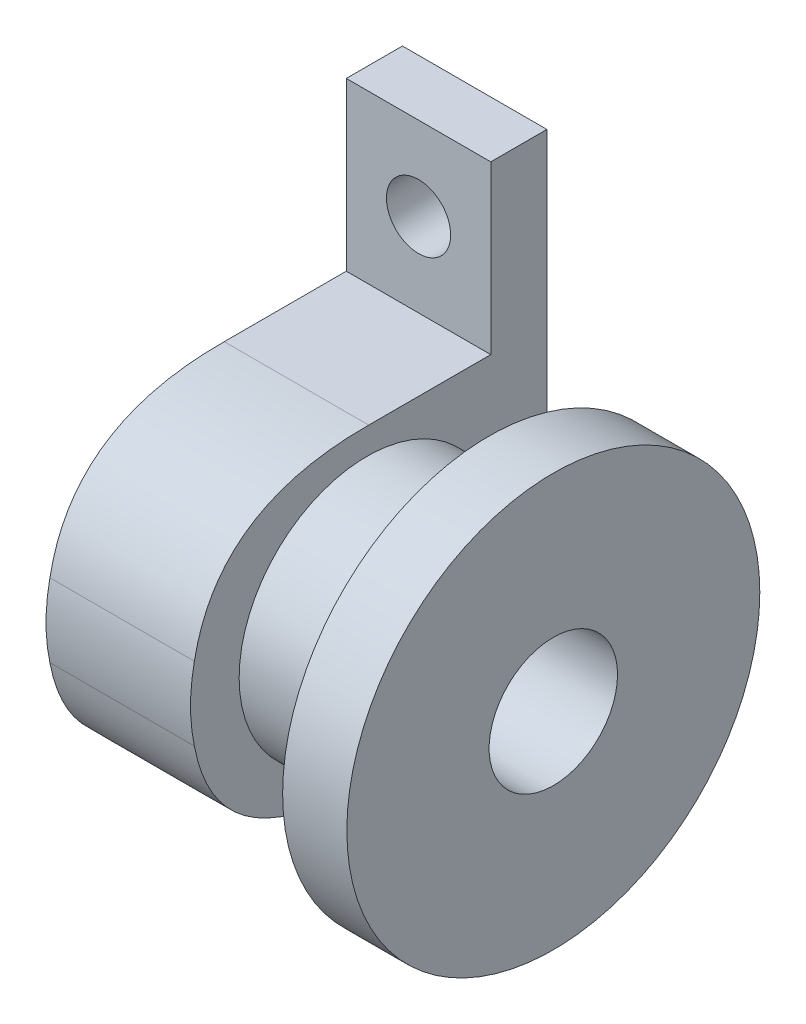
SolidWorks part; units mm, degrees
ref_plane "Front Plane" through (0, 0, 0) normal (1, 0, 0) x (0, 1, 0)
ref_plane "Top Plane" through (0, 0, 0) normal (0, 0, 1) x (0, 1, 0)
ref_plane "Right Plane" through (0, 0, 0) normal (0, 1, 0) x (-1, 0, 0)
sketch "Sketch1" plane through (0, 0, 0) normal (0, 0, 1) x (0, 1, 0)
  line L0 (-50, 0) -> (50, 0)
  line L1 (-50, 0) -> (-50, -22.5)
  line L2 (-50, -22.5) -> (50, -22.5)
  line L3 (50, -22.5) -> (50, 0)
  point P4 (0, 0)
  dimension "D1" = 100
  dimension "D2" = 22.5
extrude "Boss-Extrude1" add sketch "Sketch1" along normal blind 55.5
sketch "Sketch2" plane through (22.5, 0, 0) normal (1, 0, 0) x (0, 1, 0)
  line L0 (0, 0) -> (0, 0.5)
  line L1 (-24, 0) -> (-24, 55.5)
  line L2 (-50, 0) -> (50, 0) construction
  line L4 (-50, 55.5) -> (-50, 0) construction
  line L5 (50, 55.5) -> (50, 0) construction
  line L6 (19.6311, 8.742) -> (50, 8.742)
  line L8 (50, 55.5) -> (50, 14.5743)
  line L10 (-50, 55.5) -> (50, 55.5) construction
  line L12 (24, 0) -> (24, 55.5)
  line L13 (0, 0.5) -> (0, 55.5)
  line L14 (-24, 8.742) -> (-19.6311, 8.742)
  line L15 (-24, 8.742) -> (-50, 8.742)
  circle A4 centre (0, 28) radius 27.5
  circle A5 centre (0, 28) radius 10
  spline S0 degree 2 poles (0, 55.5) (-24.2004, 54.7772) (-24, 27.75) knots 0 0 0 1 1 1
  spline S1 degree 2 poles (0, 55.5) (24.2004, 54.7772) (24, 27.75) knots 0 0 0 1 1 1
  line M7 (50, 0) -> (50, 55.5)
  line M8 (50, 55.5) -> (-50, 55.5)
  line M9 (-50, 55.5) -> (-50, 0)
  dimension "D2" = 20
  dimension "D1" = 0.5
extrude "Cut-Extrude1" cut sketch "Sketch2" against normal through all contours A4 L1 L15 M8 M9 | S0 L1 A4 | S0 A4 L1 | S0 A4 L1 M8 | L13 A5 | L13 A5 | A4 S1 L12 M8 | A4 L12 L6 M7 M8 | L12 S1 A4 | A4 S1 L12
sketch "Sketch3" plane through (0, 0, 8.742) normal (0, 0, 1) x (1, 0, 0)
  line L0 (22.5, 50) -> (0, 24)
  circle A0 centre (11.25, 37) radius 5
  dimension "D1" = 10
extrude "Cut-Extrude2" cut sketch "Sketch3" against normal through all contours L0 A0 | L0 A0 region at (12.8546, 35.6114, 8.742) region at (9.6454, 38.3886, 8.742)
sketch "Sketch5" plane through (0, 0, 8.742) normal (0, 0, 1) x (1, 0, 0)
  line L0 (0, -24) -> (22.5, -50)
  circle A0 centre (11.25, -37) radius 4.9984
extrude "Cut-Extrude3" cut sketch "Sketch5" against normal through all contours L0 A0 | L0 A0 region at (12.8541, -35.6118, 8.742) region at (9.6459, -38.3882, 8.742)
sketch "Sketch6" plane through (0, 0, 0) normal (-1, 0, 0) x (0, -1, 0)
  circle A0 centre (0, 28) radius 12
  circle M1 centre (0, 28) radius 10
  dimension "D1" = 24
extrude "Boss-Extrude2" add sketch "Sketch6" along normal blind 5 contours A0 M1 region at (0, 11.6606, 28)
sketch "Sketch7" plane through (22.5, 0, 0) normal (1, 0, 0) x (0, 1, 0)
  circle A1 centre (0, 28) radius 19.9274
  point P4 (12.7333, 23.4598)
  circle M1 centre (0, 28) radius 10
extrude "Boss-Extrude3" add sketch "Sketch7" along normal blind 19 contours M1 region at (22.5, -19.3638, 28)
sketch "Sketch9" plane through (41.5, 0, 0) normal (1, 0, 0) x (0, 1, 0)
  circle A0 centre (0, 28) radius 32.1557
  circle A1 centre (0, 28) radius 10
extrude "Boss-Extrude5" add sketch "Sketch9" along normal blind 10
split "Split1" bodies to split 108 resulting bodies 109 110 split by face at (22.5, 0, 8.0726)
